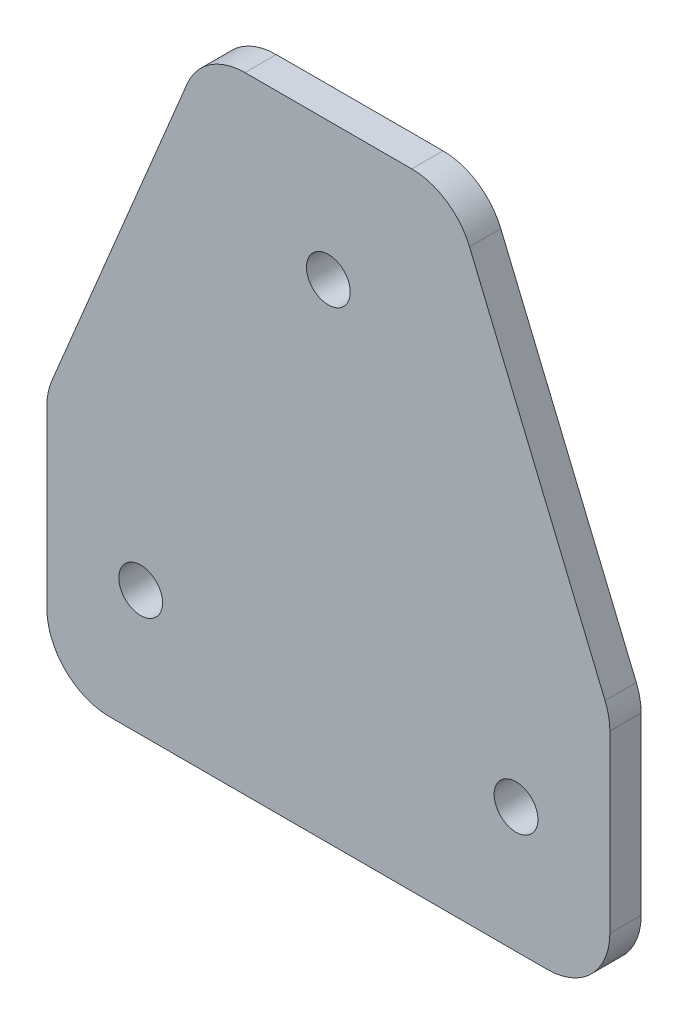
SolidWorks part; units mm, degrees
other "Objet de détail1"
ref_plane "Plan de face" through (0, 0, 0) normal (0, 0, 1) x (1, 0, 0)
ref_plane "Plan de dessus" through (0, 0, 0) normal (0, 1, 0) x (1, 0, 0)
ref_plane "Plan de droite" through (0, 0, 0) normal (1, 0, 0) x (0, 0, -1)
sketch "Esquisse1" plane through (0, 0, 0) normal (0, 0, 1) x (1, 0, 0)
  line L0 (90, 0) -> (90, 40)
  line L1 (90, 40) -> (65, 100)
  line L2 (65, 100) -> (25, 100)
  line L3 (90, 0) -> (0, 0)
  line L4 (45, 100) -> (45, 0) construction
  line L5 (0, 40) -> (25, 100)
  line L6 (0, 0) -> (0, 40)
  point P9 (72.6092, 100)
  dimension "D1" = 100
  dimension "D2" = 90
  dimension "D3" = 40
  dimension "D4" = 40
extrude "Boss.-Extru.1" add sketch "Esquisse1" along normal blind 5
sketch "Esquisse2" plane through (0, 0, 5) normal (0, 0, 1) x (1, 0, 0)
  line L5 (0, 20) -> (90, 20) construction
  line L6 (0, 40) -> (0, 0) construction
  line L7 (90, 0) -> (90, 40) construction
  line L8 (45, 20) -> (45, 0) construction
  line L9 (0, 0) -> (90, 0) construction
  line L10 (45, 78) -> (45, 20) construction
  circle A0 centre (15, 20) radius 3.5
  circle A1 centre (75, 20) radius 3.5
  circle A2 centre (45, 78) radius 3.5
  dimension "D2" = 60
  dimension "D3" = 58
  dimension "D4" = 7
  dimension "D1" = 7
extrude "Enlèv. mat.-Extru.1" cut sketch "Esquisse2" against normal through all both and the other way through all
fillet "Congé1" radius 10 6 edges at (25, 100, 2.5) (65, 100, 2.5) (90, 40, 2.5) (90, 0, 2.5) (0, 0, 2.5) (0, 40, 2.5)
